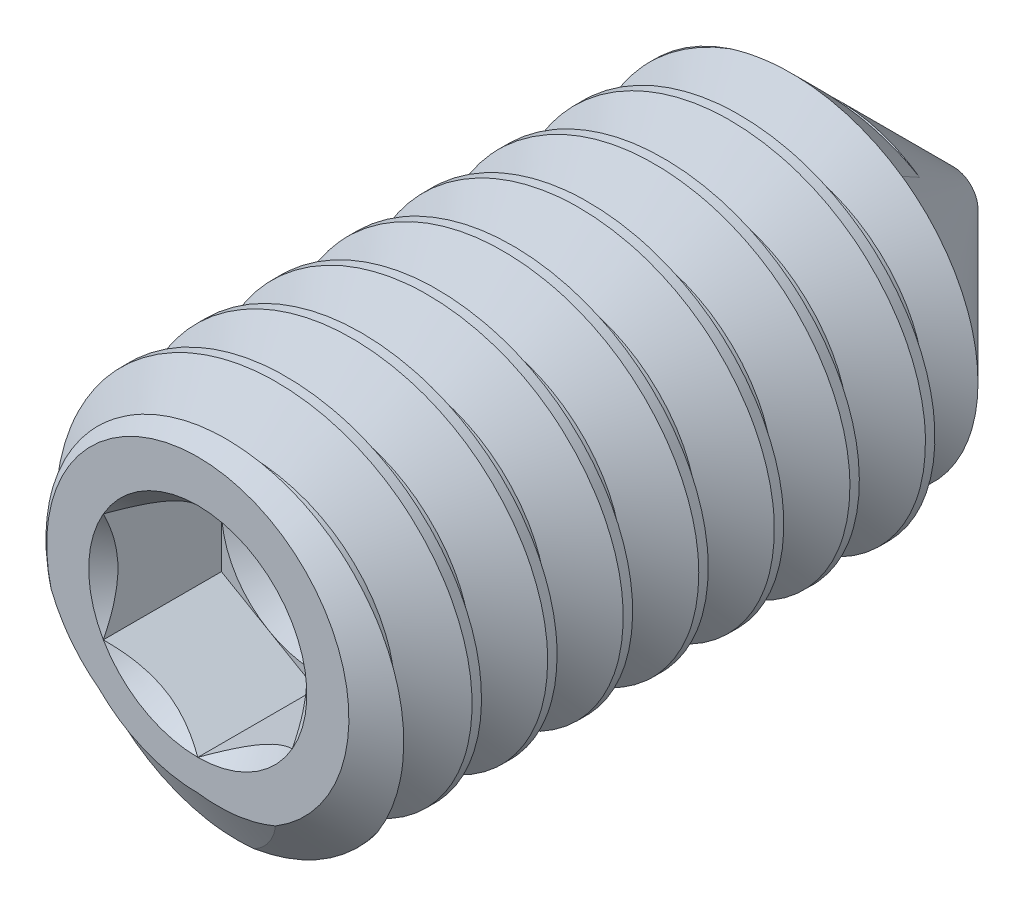
SolidWorks part; units mm, degrees
ref_plane "Front" through (0, 0, 0) normal (0, 0, 1) x (1, 0, 0)
ref_plane "Top" through (0, 0, 0) normal (0, 1, 0) x (1, 0, 0)
ref_plane "Right" through (0, 0, 0) normal (1, 0, 0) x (0, 0, -1)
sketch "Sketch22" plane through (0, 0, 0) normal (1, 0, 0) x (0, 0, -1)
  line L0 (-6.35, 0) -> (-6.35, 2.54)
  line L1 (-6.35, 2.54) -> (-5.9054, 3.175)
  line L2 (-5.9054, 3.175) -> (3.5877, 3.175)
  line L3 (3.5877, 3.175) -> (6.35, 0.4127)
  line L4 (-6.35, 2.54) -> (-6.35, -2.54) construction
  line L5 (6.35, 0) -> (-6.35, 0)
  line L6 (0, 3.175) -> (0, -3.175) construction
  line L8 (6.35, 0.4127) -> (6.35, 0)
  line L9 (-6.35, -3.175) -> (6.35, -3.175) construction
  line L10 (6.35, 0.4127) -> (6.35, -0.4128) construction
  line L11 (6.35, -0.4128) -> (3.5877, -3.175) construction
  line L13 (6.35, 0.4127) -> (5.9372, 0) construction
  line L15 (5.9372, 0) -> (6.35, -0.4128) construction
  dimension "D3" = 35
  dimension "D7" = 5.08
  dimension "Dia" = 6.35
  dimension "Length" = 12.7
  dimension "D2" = 0.8255
  dimension "D1" = 90
  dimension "D4" = 90
revolve "Revolve1" add sketch "Sketch22" angle 360 about L5
ref_plane "Plane1" through (0, 0, -6.35) normal (0, 0, 1) x (1, 0, 0)
sketch "Sketch27" plane through (0, 0, -6.35) normal (0, 0, 1) x (1, 0, 0)
  circle A0 centre (0, 0) radius 3.175 construction
  circle A1 centre (0, 0) radius 3.175
curve "Helix/Spiral1" pitch 1.27 height 13.97 radius 3.175 centre (0, 0, -6.35) axis (0, 0, 1) start towards (0, 1, 0)
sketch "Sketch28" plane through (0, 0, 0) normal (1, 0, 0) x (0, 0, -1)
  line L0 (6.35, 3.175) -> (7.4612, 3.175)
  line L1 (7.4612, 3.175) -> (6.985, 2.3501)
  line L2 (6.985, 2.3501) -> (6.8262, 2.3501)
  line L3 (6.8262, 2.3501) -> (6.35, 3.175)
  line L4 (6.5881, 2.7626) -> (7.2231, 2.7626) construction
  line L6 (-5.9054, 3.175) -> (3.5877, 3.175) construction
  line L7 (6.35, 3.4925) -> (6.35, -3.4925) construction
  dimension "D1" = 0.1588
  dimension "D3" = 60
  dimension "D2" = 0.635
sweep "Cut-Sweep2" cut profiles "Sketch28" path "Helix/Spiral1" align with end faces yes
sketch "Sketch23" plane through (0, 0, 6.35) normal (0, 0, 1) x (1, 0, 0)
  line L1 (0, 1.8331) -> (-1.5875, 0.9165)
  line L2 (-1.5875, 0.9165) -> (-1.5875, -0.9165)
  line L3 (-1.5875, -0.9165) -> (0, -1.8331)
  line L4 (0, -1.8331) -> (1.5875, -0.9165)
  line L5 (1.5875, -0.9165) -> (1.5875, 0.9165)
  line L6 (1.5875, 0.9165) -> (0, 1.8331)
  circle A0 centre (0, 0) radius 1.5875 construction
  dimension "Hex" = 3.175
extrude "Cut-Extrude10" cut sketch "Sketch23" against normal blind 1.9844
sketch "Sketch24" plane through (0, 0, 6.35) normal (0, 0, 1) x (1, 0, 0)
  circle A0 centre (0, 0) radius 1.8331
extrude "Cut-Extrude11" cut sketch "Sketch24" against normal through all draft 45
sketch "Sketch26" plane through (0, 0, 4.3656) normal (0, 0, 1) x (1, 0, 0)
  circle A0 centre (0, 0) radius 1.5875 construction
  circle A1 centre (0, 0) radius 1.5875
extrude "Cut-Extrude12" cut sketch "Sketch26" against normal through all draft 60
sketch "Sketch30" plane through (0, 0, 0) normal (1, 0, 0) x (0, 0, -1)
  line L0 (-5.9054, 3.175) -> (3.5877, 3.175) construction
  line L1 (-6.35, 0) -> (-6.35, 2.54) construction
  line L3 (-6.35, -3.175) -> (6.35, -3.175) construction
  point P0 (-6.35, 3.175)
  point P1 (3.5877, 3.175)
  point P2 (3.5877, -3.175)
  point P11 (1.6827, -3.175)
  dimension "D1" = 1.905
equation "\"D7@Sketch22\"=\"Dia@Sketch22\"*.8"
equation "\"D1@Sketch28\" = \"D4@Helix/Spiral1\" * .125"
equation "\"D3@Helix/Spiral1\" = \"Length@Sketch22\" + \"D4@Helix/Spiral1\""
equation "\"D1@Sketch30\" = \"D4@Helix/Spiral1\" * 1.5"
equation "\"hex Depth@Cut-Extrude10\" = \"Hex@Sketch23\" * .625"
equation "\"D2@Sketch28\" = \"D4@Helix/Spiral1\" * .5"
equation "\"D2@Sketch22\" = \"Dia@Sketch22\" * .13"
equation "\"D4@Sketch22\" = \"D1@Sketch22\""
